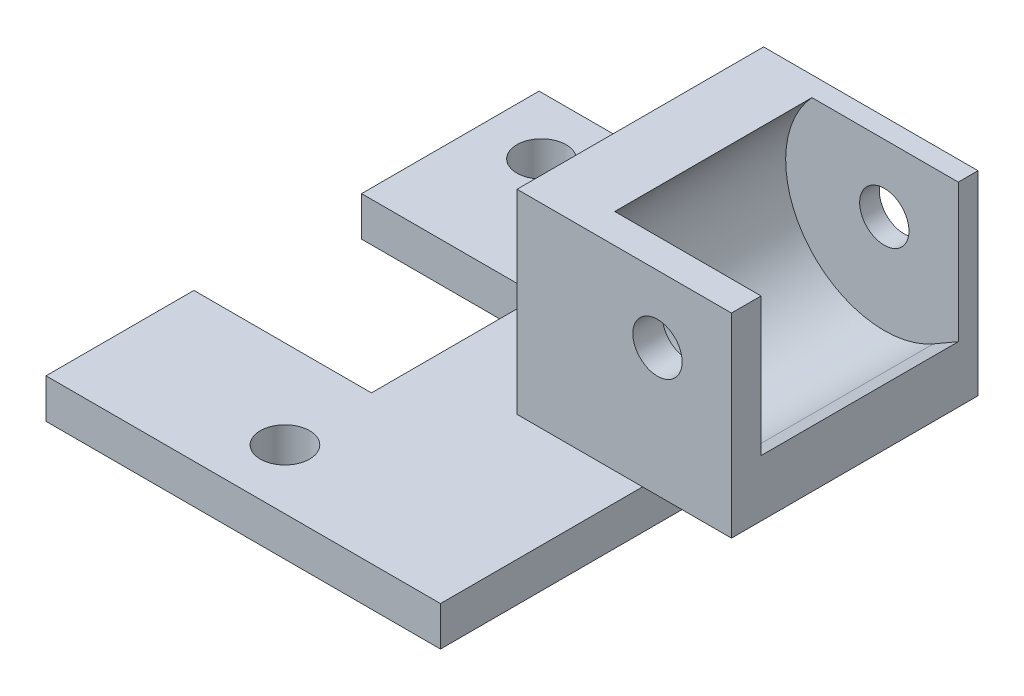
SolidWorks part; units mm, degrees
ref_plane "Front Plane" through (0, 0, 0) normal (0, 0, 1) x (1, 0, 0)
ref_plane "Top Plane" through (0, 0, 0) normal (0, 1, 0) x (1, 0, 0)
ref_plane "Right Plane" through (0, 0, 0) normal (1, 0, 0) x (0, 0, -1)
sketch "Sketch1" plane through (0, 0, 0) normal (0, 0, 1) x (1, 0, 0)
  line L0 (-527.7276, 348.6336) -> (-500.1158, 348.6336)
  line L1 (-500.1158, 348.6336) -> (-500.1158, 323.526)
  line L2 (-500.1158, 323.526) -> (-527.7276, 323.526)
  line L3 (-527.7276, 323.526) -> (-527.7276, 348.6336)
  line L4 (-471.0414, 347.5416) -> (-503.3159, 328.9895) construction
  line L5 (-471.0414, 347.5416) -> (-503.3159, 328.9895)
  arc A0 (-508.6898, 327.336) -> (-503.3159, 328.9895) centre (-509.645, 340) ccw construction
  arc A1 (-515.9742, 351.0105) -> (-520.1076, 347.199) centre (-509.645, 340) ccw construction
  arc A2 (-520.1076, 347.199) -> (-508.6898, 327.336) centre (-509.645, 340) ccw construction
  arc A3 (-508.6898, 327.336) -> (-503.3159, 328.9895) centre (-509.645, 340) ccw
  arc A4 (-515.9742, 351.0105) -> (-520.1076, 347.199) centre (-509.645, 340) ccw
  arc A5 (-520.1076, 347.199) -> (-508.6898, 327.336) centre (-509.645, 340) ccw
  dimension "D1" = 3.81
  dimension "D2" = 7.62
  dimension "D3" = 25.1076
  dimension "D4" = 27.6118
extrude "Boss-Extrude1" add sketch "Sketch1" against normal blind 27.94 contours A5 A4 L0 L3 L2 L1 L5 A3 region at (-523.3433, 348.2604, 0)
sketch "Sketch2" plane through (0, 0, -25.4) normal (0, 0, -1) x (-1, 0, 0)
  line L0 (500.1158, 330.829) -> (500.1158, 348.6336)
  line L1 (500.1158, 348.6336) -> (518.9591, 348.6336)
  line L2 (500.1158, 330.829) -> (503.3159, 328.9895) construction
  line L3 (500.1158, 330.829) -> (503.3159, 328.9895)
  arc A0 (503.3159, 328.9895) -> (518.9591, 348.6336) centre (509.645, 340) ccw construction
  arc A1 (503.3159, 328.9895) -> (518.9591, 348.6336) centre (509.645, 340) ccw
  circle A2 centre (509.645, 340) radius 3.175
  dimension "D1" = 6.35
extrude "Boss-Extrude2" add sketch "Sketch2" along normal up to surface (2.54 mm away) up to face at (-514.4007, 332.9024, -27.94)
sketch "Sketch3" plane through (0, 0, 0) normal (0, 0, 1) x (1, 0, 0)
  line L0 (-527.7276, 348.6336) -> (-500.1158, 348.6336)
  line L1 (-500.1158, 348.6336) -> (-500.1158, 323.526)
  line L2 (-500.1158, 323.526) -> (-527.7276, 323.526)
  line L3 (-527.7276, 323.526) -> (-527.7276, 348.6336)
  circle A0 centre (-509.645, 340) radius 3.175
  dimension "D1" = 6.35
extrude "Boss-Extrude3" add sketch "Sketch3" along normal blind 3.81 contours L3 L0 L1 L2 | A0
ref_plane "Plane1" through (0, 323.526, 0) normal (0, 1, 0) x (1, 0, 0)
sketch "Sketch4" plane through (0, 323.526, 0) normal (0, 1, 0) x (1, 0, 0)
  line L1 (-562.3598, 33.6602) -> (-511.5598, 33.7024)
  line L2 (-562.3598, 33.6602) -> (-562.3598, -29.8398)
  line L3 (-562.3598, -29.8398) -> (-511.5598, -29.8398)
  line L4 (-511.5598, 33.7024) -> (-511.5598, -29.8398)
  circle A0 centre (-539.2691, -22.1596) radius 3.175
  circle A1 centre (-554.6451, 26.2575) radius 3.175
  dimension "D5" = 50.8
  dimension "D9" = 6.35
  dimension "D10" = 6.35
  dimension "D2" = 63.5
  dimension "D3" = 63.5422
  dimension "D4" = 50.8
  dimension "D6" = 7.7147
  dimension "D7" = 7.6801
  dimension "D8" = 23.0907
extrude "Boss-Extrude4" add sketch "Sketch4" against normal blind 5.08
sketch "Sketch5" plane through (0, 323.526, 0) normal (0, 1, 0) x (1, 0, 0)
  line L0 (-562.3598, 10.8002) -> (-539.4998, 10.8002)
  line L1 (-562.3598, 33.6602) -> (-562.3598, -29.8398) construction
  line L2 (-539.4998, 10.8002) -> (-539.4998, -10.7898)
  line L3 (-539.4998, -10.7898) -> (-562.3598, -10.7898)
  line L4 (-562.3598, -10.7898) -> (-562.3598, 10.8002)
  line L7 (-562.3598, -29.8398) -> (-511.5598, -29.8398) construction
  dimension "D1" = 22.86
  dimension "D2" = 21.59
  dimension "D3" = 19.05
extrude "Cut-Extrude1" cut sketch "Sketch5" against normal through all
